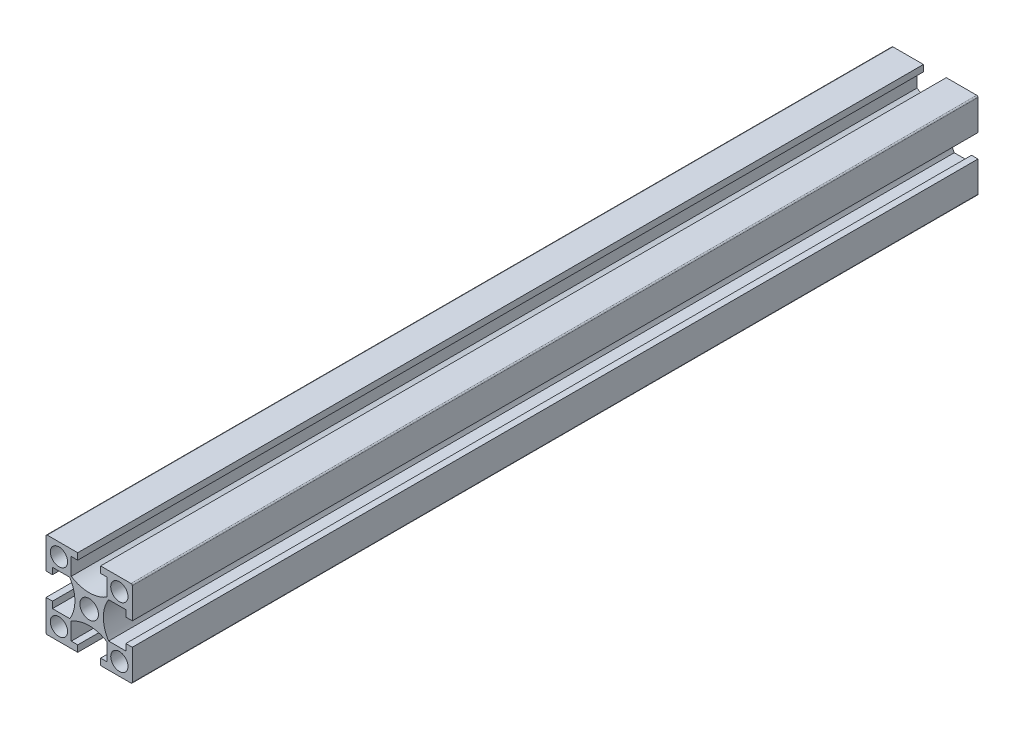
SolidWorks part; units mm, degrees
material "3.0255 (EN-AW 1350A)"
ref_plane "정면" through (0, 0, 0) normal (0, 0, 1) x (1, 0, 0)
ref_plane "윗면" through (0, 0, 0) normal (0, 1, 0) x (1, 0, 0)
ref_plane "우측면" through (0, 0, 0) normal (1, 0, 0) x (0, 0, -1)
sketch "스케치1" plane through (0, 0, 0) normal (0, 0, 1) x (1, 0, 0)
  line L0 (0, 32.0265) -> (0, -31.6588) construction
  line L1 (-10, 10) -> (-10, -10)
  line L2 (-10, 10) -> (10, 10)
  line L3 (-10, 2.65) -> (-8.5, 2.65)
  line L4 (13.6618, 0) -> (-11.6993, 0) construction
  line L5 (-8.5, 2.65) -> (-8.5, 4.15)
  line L6 (-8.5, 4.15) -> (-4.5032, 4.15)
  line L7 (-10, -2.65) -> (-8.5, -2.65)
  line L8 (-8.5, -2.65) -> (-8.5, -4.15)
  line L9 (-8.5, -4.15) -> (-4.5032, -4.15)
  line L10 (-10, -10) -> (10, -10)
  line L11 (10, 10) -> (10, -10)
  circle A0 centre (-7, 7) radius 2
  circle A1 centre (-7, -7) radius 2
  arc A2 (-4.5032, 4.15) -> (-4.5032, -4.15) centre (-11.0587, 0) cw
  circle A3 centre (0, 0) radius 2.15
  circle A4 centre (7, 7) radius 2
  circle A5 centre (7, -7) radius 2
  point P21 (-10, 0)
  point P23 (-3.3, 0)
  point P31 (0, -10)
  point P32 (0, 10)
  dimension "D3" = 4
  dimension "D9" = 6.7
  dimension "D10" = 4.3
  dimension "D11" = 7.7587
  dimension "D1" = 20
  dimension "D2" = 20
  dimension "D4" = 14
  dimension "D5" = 14
  dimension "D6" = 5.3
  dimension "D7" = 8.3
  dimension "D8" = 1.5
extrude "보스-돌출1" add sketch "스케치1" along normal blind 196 contours A0 | A4 | A3 | A5 | A1 | A2 L6 L5 L3 L1 L7 L8 L9 | L2 L11 L10 L1 region at (-6.6069, 0, 0) region at (-7, 7, 0) region at (-7, -7, 0) region at (0, 0, 0) region at (7, 7, 0) region at (7, -7, 0)
extrude "컷-돌출1" cut sketch "스케치1<3>" along normal up to next contours A2 L6 L5 L3 L1 L7 L8 L9 region at (-6.6069, 0, 0)
sketch "스케치1<3>" plane through (0, 0, 0) normal (0, 0, 1) x (1, 0, 0) same geometry as "스케치1"
pattern_circular "원형 패턴1" count 4 over 360 about axis through (0, 0, 196) along (0, 0, -1) of "컷-돌출1" reverse direction yes
fillet "필렛1" radius 0.3 4 edges at (10, -10, 98) (-10, -10, 98) (-10, 10, 98) (10, 10, 98)
sketch "스케치4" plane through (0, -10, 0) normal (0, -1, 0) x (1, 0, 0)
  line L1 (4.15, 196) -> (-4.15, 196) construction
  circle A0 centre (0, 98) radius 2.5
  dimension "D1" = 98
extrude "컷-돌출4" cut sketch "스케치4" against normal through all
